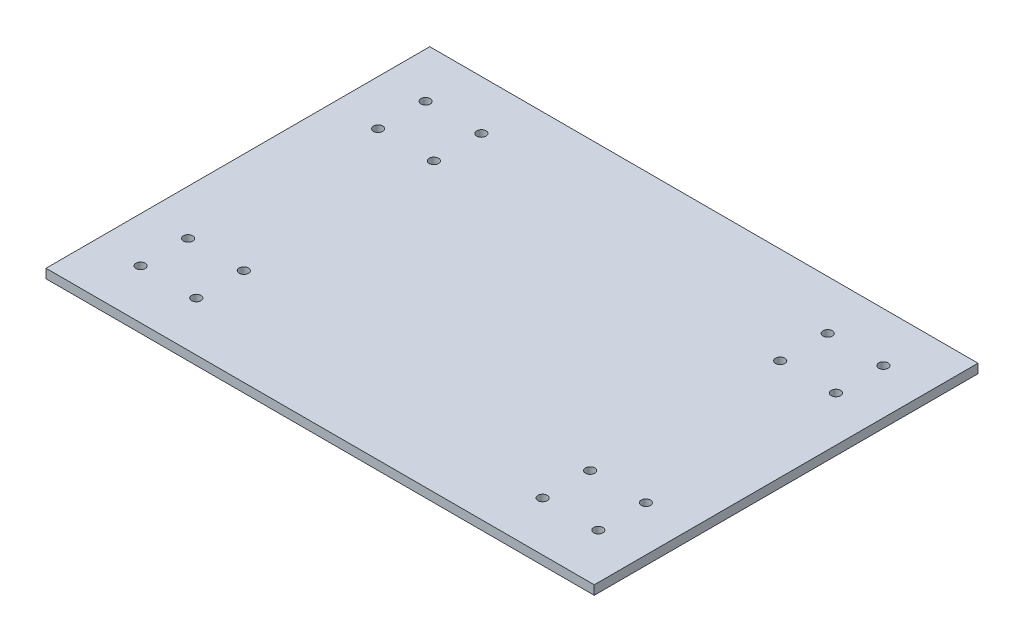
SolidWorks part; units mm, degrees
ref_plane "Front Plane" through (0, 0, 0) normal (0, 0, 1) x (1, 0, 0)
ref_plane "Top Plane" through (0, 0, 0) normal (0, 1, 0) x (1, 0, 0)
ref_plane "Right Plane" through (0, 0, 0) normal (1, 0, 0) x (0, 0, -1)
sketch "Sketch1" plane through (0, 0, 0) normal (0, 1, 0) x (1, 0, 0)
  line L1 (-150, -105) -> (150, -105)
  line L2 (-150, -105) -> (-150, 105)
  line L3 (-150, 105) -> (150, 105)
  line L4 (150, -105) -> (150, 105)
  line L5 (-150, -105) -> (150, 105) construction
  line L6 (-150, 105) -> (150, -105) construction
  point P0 (0, 0)
  dimension "D1" = 300
  dimension "D2" = 210
extrude "Boss-Extrude1" add sketch "Sketch1" along normal mid plane 5
sketch "Sketch2" plane through (0, 2.5, 0) normal (0, 1, 0) x (1, 0, 0)
  line L5 (-110, 105) -> (-110, -105)
  line L6 (-110, 105) -> (-110, -105) construction
  line L8 (110, -105) -> (110, 105)
  line L9 (110, -105) -> (110, 105) construction
  line L11 (150, 65) -> (-150, 65)
  line L12 (150, 65) -> (-150, 65) construction
  line L14 (-150, -65) -> (150, -65)
  line L15 (-150, -65) -> (150, -65) construction
  line L16 (-125.25, 78) -> (-94.75, 78) construction
  line L17 (-125.25, 78) -> (-125.25, 52) construction
  line L18 (-125.25, 52) -> (-94.75, 52) construction
  line L19 (-94.75, 78) -> (-94.75, 52) construction
  line L20 (-125.25, 78) -> (-94.75, 52) construction
  line L21 (-125.25, 52) -> (-94.75, 78) construction
  line L22 (94.75, 52) -> (125.25, 52) construction
  line L23 (94.75, 52) -> (94.75, 78) construction
  line L24 (94.75, 78) -> (125.25, 78) construction
  line L25 (125.25, 52) -> (125.25, 78) construction
  line L26 (94.75, 52) -> (125.25, 78) construction
  line L27 (94.75, 78) -> (125.25, 52) construction
  line L28 (94.75, -52) -> (125.25, -52) construction
  line L29 (94.75, -52) -> (94.75, -78) construction
  line L30 (94.75, -78) -> (125.25, -78) construction
  line L31 (125.25, -52) -> (125.25, -78) construction
  line L32 (94.75, -52) -> (125.25, -78) construction
  line L33 (94.75, -78) -> (125.25, -52) construction
  line L34 (-125.25, -78) -> (-94.75, -78) construction
  line L35 (-125.25, -78) -> (-125.25, -52) construction
  line L36 (-125.25, -52) -> (-94.75, -52) construction
  line L37 (-94.75, -78) -> (-94.75, -52) construction
  line L38 (-125.25, -78) -> (-94.75, -52) construction
  line L39 (-125.25, -52) -> (-94.75, -78) construction
  circle A0 centre (-125.25, 78) radius 2.55
  circle A1 centre (-125.25, 52) radius 2.55
  circle A2 centre (-94.75, 78) radius 2.55
  circle A3 centre (-94.75, 52) radius 2.55
  circle A4 centre (-125.25, -52) radius 2.55
  circle A5 centre (-125.25, -78) radius 2.55
  circle A6 centre (-94.75, -78) radius 2.55
  circle A7 centre (-94.75, -52) radius 2.55
  circle A8 centre (125.25, -52) radius 2.55
  circle A9 centre (94.75, -52) radius 2.55
  circle A10 centre (94.75, -78) radius 2.55
  circle A11 centre (125.25, -78) radius 2.55
  circle A12 centre (94.75, 78) radius 2.55
  circle A13 centre (94.75, 52) radius 2.55
  circle A14 centre (125.25, 78) radius 2.55
  circle A15 centre (125.25, 52) radius 2.55
  point P0 (-110, 65)
  point P13 (110, 65)
  point P18 (110, -65)
  point P23 (-110, -65)
  dimension "D13" = 5.1
  dimension "D14" = 5.1
  dimension "D15" = 5.1
  dimension "D16" = 5.1
  dimension "D17" = 5.1
  dimension "D18" = 5.1
  dimension "D19" = 5.1
  dimension "D20" = 5.1
  dimension "D21" = 5.1
  dimension "D22" = 5.1
  dimension "D23" = 5.1
  dimension "D24" = 5.1
  dimension "D25" = 5.1
  dimension "D26" = 5.1
  dimension "D27" = 5.1
  dimension "D28" = 5.1
  dimension "D1" = 40
  dimension "D5" = 30.5
  dimension "D6" = 26
  dimension "D7" = 30.5
  dimension "D8" = 26
  dimension "D9" = 26
  dimension "D10" = 30.5
  dimension "D11" = 26
  dimension "D12" = 30.5
  dimension "D2" = 40
  dimension "D3" = 40
  dimension "D4" = 40
extrude "Cut-Extrude1" cut sketch "Sketch2" against normal through all
